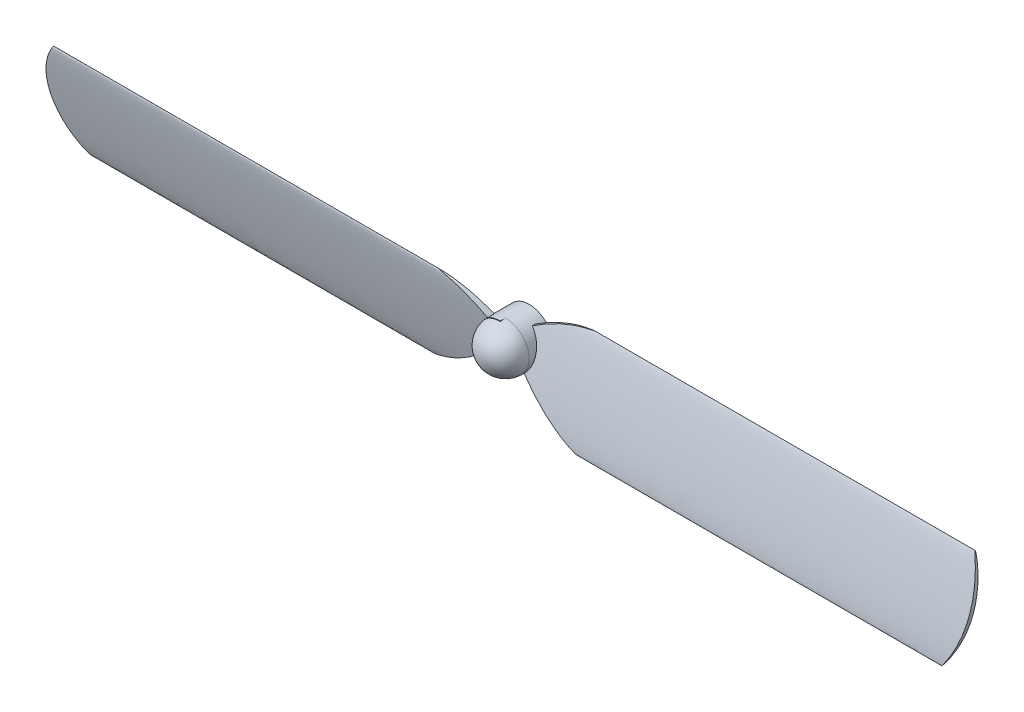
SolidWorks part; units mm, degrees
ref_plane "Plan de face" through (0, 0, 0) normal (0, 0, 1) x (1, 0, 0)
ref_plane "Plan de dessus" through (0, 0, 0) normal (0, 1, 0) x (1, 0, 0)
ref_plane "Plan de droite" through (0, 0, 0) normal (1, 0, 0) x (0, 0, -1)
sketch "Esquisse1" plane through (0, 0, 0) normal (0, 0, 1) x (1, 0, 0)
  circle A0 centre (0, 0) radius 5
  dimension "D1" = 10
extrude "Boss.-Extru.1" add sketch "Esquisse1" along normal blind 10
sketch "Esquisse2" plane through (0, 0, 0) normal (0, 0, -1) x (-1, 0, 0)
  circle A0 centre (0, 0) radius 2.5
  dimension "D1" = 5
extrude "Enlèv. mat.-Extru.1" cut sketch "Esquisse2" against normal blind 4
fillet "Congé2" radius 5 1 edges at (5, 0, 10)
ref_plane "Plan1" through (0, 0, 0) normal (1, 0, 0) x (0, 0, -1)
sketch "Esquisse3" plane through (0, 0, 0) normal (1, 0, 0) x (0, 0, -1)
  spline S0 degree 3 poles (-7.0209, -16.905) (3.669, 24.6443) (-5.0022, -3.7599) (-7.0209, -16.905) (3.669, 24.6443) (-5.0022, -3.7599) knots -1 -0.524883 -0.499914 0 0.475117 0.500086 1 1.475117 1.500086 2 only from (-1.0284, 7.7445) to (-1.0284, 7.7445)
extrude "Boss.-Extru.2" add sketch "Esquisse3" along normal blind 100
sketch "Esquisse4" plane through (0, 0, 0) normal (1, 0, 0) x (0, 0, -1)
  spline S0 degree 3 poles (-1.4434, -17.7486) (-11.3063, 26.1944) (-1.4418, -4.3249) (-1.4434, -17.7486) (-11.3063, 26.1944) (-1.4418, -4.3249) knots -1 -0.511223 -0.49981 0 0.488777 0.50019 1 1.488777 1.50019 2 only from (-6.4301, 7.8631) to (-6.4301, 7.8631)
extrude "Boss.-Extru.3" add sketch "Esquisse4" against normal blind 100
ref_plane "Plan2" through (0, 0, 0) normal (0, 0, 1) x (1, 0, 0)
sketch "Esquisse6" plane through (0, 0, 0) normal (0, 0, 1) x (1, 0, 0)
  line L1 (0, 8.2759) -> (-100, 8.2759) construction
  line L2 (100, 8.0969) -> (0, 8.0969) construction
  arc A0 (3.14, 3.8911) -> (-2.8443, 4.1122) centre (0, 0) ccw
  arc A1 (0, -5) -> (0, 5) centre (0, 0) ccw construction
  spline S0 degree 2 poles (-2.8443, 4.1122) (-8.2868, 8.1295) (-14.6774, 8.4934) knots 0 0 0 1 1 1
  spline S1 degree 2 poles (3.14, 3.8911) (10.0455, 8.1744) (17.8087, 8.2759) knots 0 0 0 1 1 1
  spline S2 degree 1 poles (-14.6774, 8.4934) (17.8087, 8.2759) knots 0 0 1 1
extrude "Enlèv. mat.-Extru.4" cut sketch "Esquisse6" along normal blind 100
sketch "Esquisse7" plane through (0, 0, 0) normal (0, 0, 1) x (1, 0, 0)
  arc A0 (-4.0249, -2.9665) -> (3.5024, -3.5683) centre (0, 0) ccw
  arc A1 (-4.9495, -0.7089) -> (0, -5) centre (0, 0) ccw construction
  spline S0 degree 2 poles (-4.0249, -2.9665) (-14.8521, -14.1841) (-28.4265, -13.2061) knots 0 0 0 1 1 1
  spline S1 degree 2 poles (3.5024, -3.5683) (14.5144, -13.7268) (27.7697, -13.2544) knots 0 0 0 1 1 1
  spline S2 degree 1 poles (-28.4265, -13.2061) (27.7697, -13.2544) knots 0 0 1 1
extrude "Enlèv. mat.-Extru.5" cut sketch "Esquisse7" along normal blind 100 contours S0 S2 S1 A0 region at (-0.1904, -9.8226, 0)
sketch "Esquisse8" plane through (0, 0, 0) normal (0, 0, 1) x (1, 0, 0)
  line L0 (-87.5215, 13.9316) -> (-110.0298, 13.9316)
  line L1 (-110.0298, 13.9316) -> (-110.0298, -20.7597)
  line L2 (-110.0298, -20.7597) -> (-87.5167, -20.7597)
  line L3 (-87.5167, -20.7597) -> (-87.5167, -13.9337)
  arc A0 (-87.5167, -13.9337) -> (-87.5215, 13.9316) centre (-81.3028, 0) cw
extrude "Enlèv. mat.-Extru.6" cut sketch "Esquisse8" along normal blind 100
sketch "Esquisse9" plane through (0, 0, 0) normal (0, 0, 1) x (1, 0, 0)
  line L0 (92.354, 12.4771) -> (114.4402, 11.0153)
  line L1 (114.4402, 11.0153) -> (114.4402, -13.9491)
  line L2 (114.4402, -13.9491) -> (87.9426, -16.2626)
  arc A0 (87.9426, -16.2626) -> (92.354, 12.4771) centre (77.8171, 0) ccw
extrude "Enlèv. mat.-Extru.7" cut sketch "Esquisse9" along normal blind 100
sketch "Esquisse10" plane through (0, 0, 0) normal (0, 0, 1) x (1, 0, 0)
  circle A0 centre (0, 0) radius 2.5
extrude "Enlèv. mat.-Extru.8" cut sketch "Esquisse10" along normal blind 7
